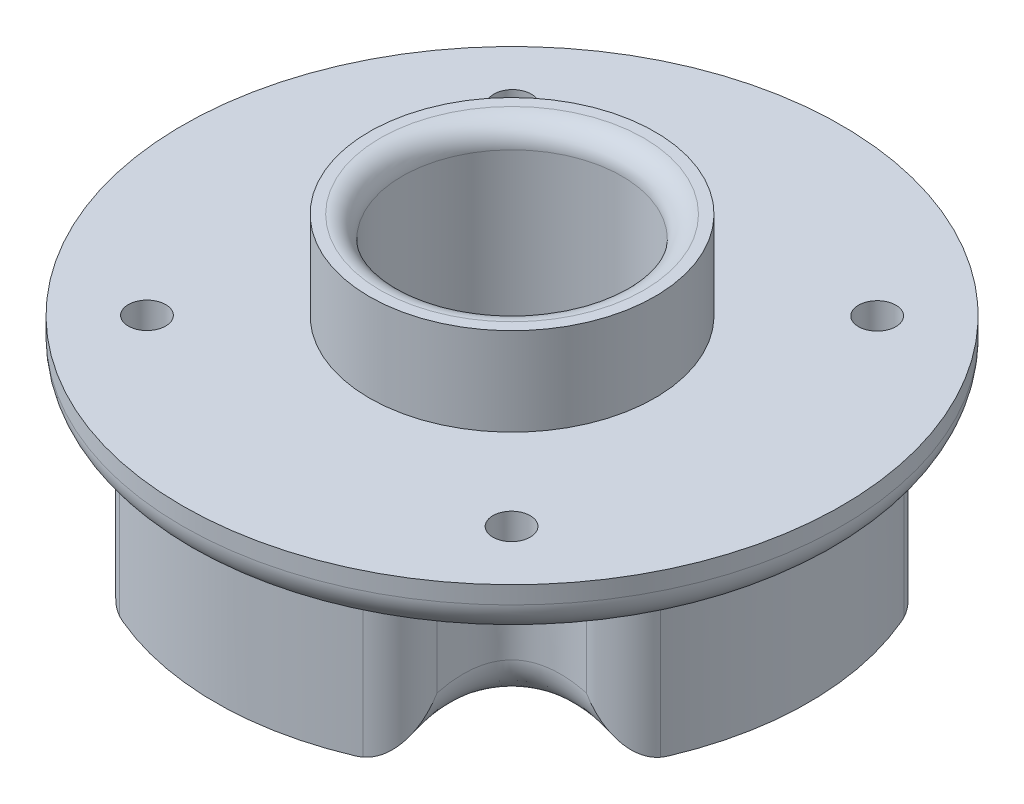
SolidWorks part; units mm, degrees
ref_plane "Front Plane" through (0, 0, 0) normal (0, 0, 1) x (1, 0, 0)
ref_plane "Top Plane" through (0, 0, 0) normal (0, 1, 0) x (1, 0, 0)
ref_plane "Right Plane" through (0, 0, 0) normal (1, 0, 0) x (0, 0, -1)
sketch "Sketch2" plane through (0, 0, 0) normal (0, 1, 0) x (1, 0, 0)
  line L0 (0, 11.75) -> (0, 13.5) construction
  circle A0 centre (0, 0) radius 10 construction
  circle A1 centre (0, 10) radius 1.75 construction
  circle A2 centre (10, 0) radius 1.75 construction
  circle A3 centre (0, 0) radius 13.5
  dimension "D1" = 3.5
  dimension "D2" = 20
  dimension "D3" = 27
  dimension "D4" = 1.75
extrude "Boss-Extrude1" add sketch "Sketch2" along normal blind 8.5
sketch "Sketch3" plane through (0, 0, 0) normal (0, -1, 0) x (1, 0, 0)
  circle A0 centre (0, 0) radius 5
extrude "Cut-Extrude1" cut sketch "Sketch3" against normal blind 8.5
sketch "Sketch4" plane through (0, 0, 0) normal (0, -1, 0) x (1, 0, 0)
  line L0 (0, 0) -> (10, 0) construction
  circle A0 centre (10, 0) radius 1.75
extrude "Cut-Extrude2" cut sketch "Sketch4" against normal blind 7
pattern_circular "CirPattern1" count 4 every 90 about axis through (0, 0, 0) along (0, -1, 0) of "Cut-Extrude2"
sketch "Sketch5" plane through (0, 0, 0) normal (0, -1, 0) x (1, 0, 0)
  line L0 (0, 0) -> (0, 13.5) construction
  line L1 (0, 13.5) -> (13.4999, 0.0376) construction
  line L2 (13.4999, 0.0376) -> (0, 0) construction
  line L3 (0, 0) -> (9.5326, 9.5592) construction
  line L4 (7.0612, 7.0809) -> (7.0612, 11.5061) construction
  line L5 (7.0612, 7.0809) -> (11.4939, 7.0809) construction
  circle A0 centre (0, 0) radius 13.5 construction
  circle A1 centre (8.2969, 8.3201) radius 1.75 construction
  arc A2 (7.0612, 11.5061) -> (11.4939, 7.0809) centre (0, 0) cw
  spline S0 degree 2 poles (7.0612, 11.5061) (4.8486, 4.8646) (11.4939, 7.0809) knots 0 0 0 1 1 1
  dimension "D1" = 11.75
  dimension "D2" = 3.5
extrude "Cut-Extrude3" cut sketch "Sketch5" against normal blind 6.2
sketch "Sketch8" plane through (0, 6.2, 0) normal (0, -1, 0) x (1, 0, 0)
  circle A0 centre (8.2969, 8.3201) radius 0.85
  dimension "D1" = 1.7
  dimension "D2" = 11.75
extrude "Cut-Extrude4" cut sketch "Sketch8" against normal blind 6.5
fillet "Fillet1" radius 2 3 edges at (11.4939, 3.1, 7.0809) (7.0612, 3.1, 11.5061)
pattern_circular "CirPattern2" count 4 every 90 about axis through (0, 0, 0) along (0, -1, 0) of "Fillet1", "Cut-Extrude4", "Cut-Extrude3"
fillet "Fillet3" radius 2 1 edges at (0, 0, -5)
sketch "Sketch9" plane through (0, 8.5, 0) normal (0, 1, 0) x (1, 0, 0)
  circle A0 centre (8.3201, 8.2969) radius 0.85 construction
  dimension "D1" = 11.75
sketch "Sketch11" plane through (0, 8.5, 0) normal (0, 1, 0) x (1, 0, 0)
  circle A1 centre (0, 0) radius 6.5
  circle A2 centre (0, 0) radius 5
extrude "Boss-Extrude2" add sketch "Sketch11" along normal blind 4
fillet "Fillet5" radius 1 1 edges at (0, 12.5, 5)
sketch "Sketch13" plane through (0, 8.5, 0) normal (0, 1, 0) x (1, 0, 0)
  circle A0 centre (0, 0) radius 13.5
  circle A1 centre (0, 0) radius 15
extrude "Boss-Extrude3" add sketch "Sketch13" against normal blind 2.3
sketch "Sketch14" plane through (0, 0, 0) normal (1, 0, 0) x (0, 0, -1)
  line L0 (-0.0116, 6.2) -> (-0.0116, 8.5) construction
  line L1 (-5.5511, 6.2) -> (5.5279, 6.2) construction
  line L2 (-7.4701, 8.5) -> (-9.1701, 8.5) construction
fillet "Fillet7" radius 1.5 1 edges at (0, 6.2, 15)
